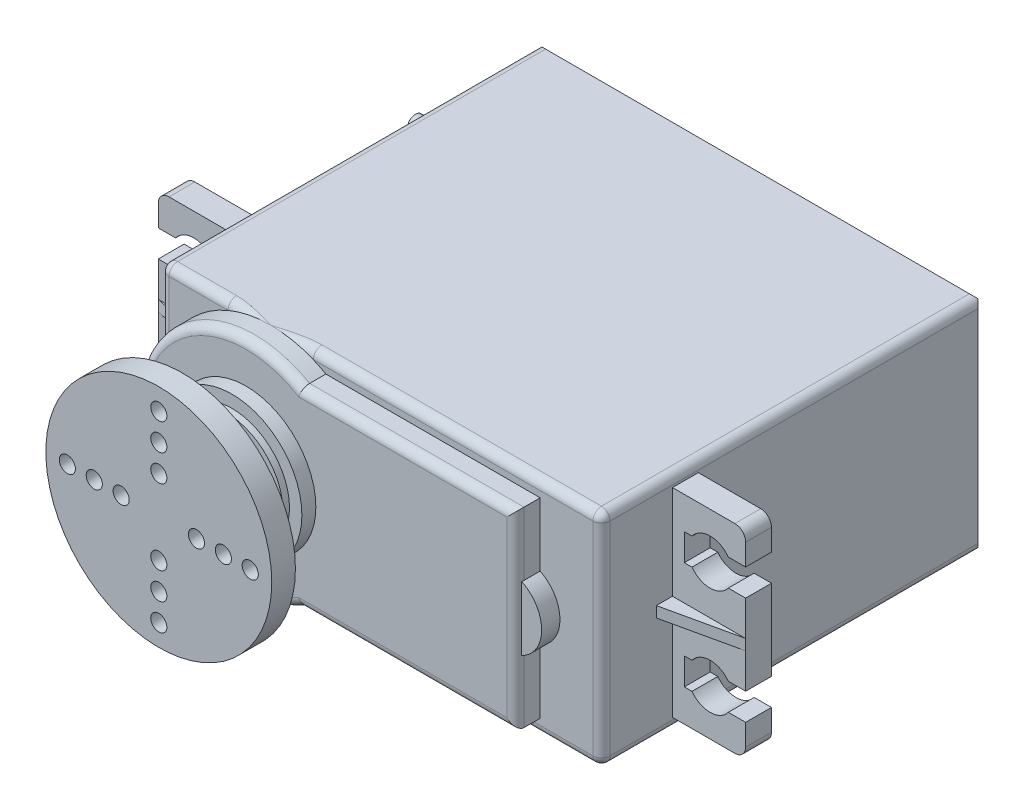
SolidWorks part; units mm, degrees
material "Cast Alloy Steel"
ref_plane "Front Plane" through (0, 0, 0) normal (0, 0, 1) x (1, 0, 0)
ref_plane "Top Plane" through (0, 0, 0) normal (0, 1, 0) x (1, 0, 0)
ref_plane "Right Plane" through (0, 0, 0) normal (1, 0, 0) x (0, 0, -1)
sketch "Sketch1" plane through (0, 0, 0) normal (0, 0, 1) x (1, 0, 0)
  line L1 (-20.5, 10.25) -> (20.5, 10.25)
  line L2 (-20.5, 10.25) -> (-20.5, -10.25)
  line L3 (-20.5, -10.25) -> (20.5, -10.25)
  line L4 (20.5, 10.25) -> (20.5, -10.25)
  line L5 (-20.5, 10.25) -> (20.5, -10.25) construction
  line L6 (-20.5, -10.25) -> (20.5, 10.25) construction
  point P0 (0, 0)
  dimension "D1" = 41
  dimension "D2" = 20.5
extrude "Boss-Extrude1" add sketch "Sketch1" along normal blind 37
chamfer "Chamfer1" distance 2 angle 45 4 edges at (-20.5, 0, 0) (0, 10.25, 0) (20.5, 0, 0) (0, -10.25, 0)
sketch "Sketch2" plane through (0, 0, 37) normal (0, 0, 1) x (1, 0, 0)
  line L0 (-20.5, 10.25) -> (-20.5, -10.25) construction
  line L1 (-5.122, 8.875) -> (14.8, 8.875)
  line L3 (-5.122, -8.875) -> (14.8, -8.875)
  line L4 (14.8, 8.875) -> (14.8, 2.9719)
  line L5 (-20.5, 0) -> (20.5, 0) construction
  line L6 (20.5, -10.25) -> (20.5, 10.25) construction
  line L7 (14.8, -2.9719) -> (14.8, -8.875)
  line L8 (14.8, 2.9719) -> (14.8, -2.9719) construction
  arc A0 (-5.122, 8.875) -> (-5.122, -8.875) centre (-10.25, 0) ccw
  arc A1 (14.8, -2.9719) -> (14.8, 2.9719) centre (13.32, 0) ccw
  dimension "D2" = 6.64
  dimension "D5" = 1.48
  dimension "D1" = 10.25
  dimension "D3" = 5.7
  dimension "D4" = 17.75
extrude "Boss-Extrude2" add sketch "Sketch2" along normal blind 2.3
sketch "Sketch3" plane through (0, 0, 39.3) normal (0, 0, 1) x (1, 0, 0)
  line L0 (14.8, 2.9719) -> (14.8, -2.9719)
  arc A0 (14.8, -2.9719) -> (14.8, 2.9719) centre (13.32, 0) ccw construction
  arc A1 (14.8, -2.9719) -> (14.8, 2.9719) centre (13.32, 0) ccw
extrude "Cut-Extrude1" cut sketch "Sketch3" against normal blind 0.6
sketch "Sketch4" plane through (0, 0, 39.3) normal (0, 0, 1) x (1, 0, 0)
  circle A0 centre (-10.25, 0) radius 6.5
  dimension "D1" = 13
extrude "Boss-Extrude3" add sketch "Sketch4" along normal blind 1.3
sketch "Sketch5" plane through (0, 0, 40.6) normal (0, 0, 1) x (1, 0, 0)
  circle A0 centre (-10.25, 0) radius 5.35
  dimension "D1" = 10.7
extrude "Boss-Extrude4" add sketch "Sketch5" along normal blind 0.6
sketch "Sketch6" plane through (0, 0, 41.2) normal (0, 0, 1) x (1, 0, 0)
  circle A0 centre (-10.25, 0) radius 3
  dimension "D1" = 6
extrude "Boss-Extrude5" add sketch "Sketch6" along normal blind 4
sketch "Sketch7" plane through (0, 0, 45.2) normal (0, 0, 1) x (1, 0, 0)
  circle A0 centre (-10.25, 0) radius 10.5
  dimension "D1" = 21
extrude "Boss-Extrude6" add sketch "Sketch7" along normal blind 2.2
sketch "Sketch8" plane through (0, 0, 47.4) normal (0, 0, 1) x (1, 0, 0)
  line L0 (-10.25, 0) -> (-20.75, 0) construction
  circle A0 centre (-10.25, 0) radius 10.5 construction
  circle A1 centre (-13.75, 0) radius 0.75
  circle A2 centre (-16.25, 0) radius 0.75
  circle A3 centre (-18.75, 0) radius 0.75
  dimension "D1" = 1.5
  dimension "D2" = 3.5
  dimension "D3" = 2.5
  dimension "D4" = 2.5
extrude "Cut-Extrude2" cut sketch "Sketch8" against normal blind 2.2
pattern_circular "CirPattern1" count 4 over 360 about axis through (-10.25, 0, 47.4) along (0, 0, -1) of "Cut-Extrude2"
sketch "Sketch9" plane through (-20.5, 0, 0) normal (-1, 0, 0) x (0, 0, 1)
  line L1 (3.2, 3.5) -> (7.4, 3.5)
  line L2 (3.2, 3.5) -> (3.2, -3.5)
  line L3 (3.2, -3.5) -> (7.4, -3.5)
  line L4 (7.4, 3.5) -> (7.4, -3.5)
  point P4 (3.2, 0)
  dimension "D1" = 7
  dimension "D2" = 4.2
  dimension "D3" = 3.2
extrude "Boss-Extrude7" add sketch "Sketch9" along normal blind 1
sketch "Sketch10" plane through (-21.5, 0, 0) normal (-1, 0, 0) x (0, 0, 1)
  line L8 (3.55, 3.15) -> (3.55, -3.15)
  line L9 (3.55, -3.15) -> (7.05, -3.15)
  line L10 (7.05, -3.15) -> (7.05, 3.15)
  line L11 (7.05, 3.15) -> (3.55, 3.15)
  line L12 (3.55, 3.15) -> (3.55, -3.15)
  line L13 (3.55, -3.15) -> (7.05, -3.15)
  line L14 (7.05, -3.15) -> (7.05, 3.15)
  line L15 (7.05, 3.15) -> (3.55, 3.15)
  dimension "D1" = 0.35
extrude "Boss-Extrude8" add sketch "Sketch10" along normal blind 4 draft 5
sketch "Sketch11" plane through (-25.5, 0, 0) normal (-1, 0, 0) x (0, 0, 1)
  line L0 (3.9, 2.8) -> (3.9, -2.8) construction
  circle A0 centre (5.3, 1.5) radius 0.75
  circle A1 centre (5.3, 0) radius 0.75
  circle A2 centre (5.3, -1.5) radius 0.75
  dimension "D1" = 1.5
  dimension "D2" = 1.4
  dimension "D3" = 1.4
  dimension "D4" = 1.4
extrude "Boss-Extrude10" add sketch "Sketch11" along normal blind 3 separate body contours A1 | A2 | A0 region at (-25.5, 1.5, 5.3) region at (-25.5, -1.5, 5.3) region at (-25.5, 0, 5.3)
fillet "Fillet1" radius 0.8 15 edges at (-20.5, -5.125, 37) (-15.375, -10.25, 37) (-15.375, 10.25, 37) (-20.5, 5.125, 37) (5.125, -10.25, 37) (20.5, 0, 37) (5.125, 10.25, 37) (14.8, 0, 39.3) (4.839, -8.875, 39.3) (-20.5, 0, 39.3) (4.839, 8.875, 39.3) (20.5, -10.25, 19.5) (20.5, 10.25, 19.5) (-20.5, 10.25, 19.5) (-20.5, -10.25, 19.5)
sketch "Sketch12" plane through (-20.5, 0, 0) normal (-1, 0, 0) x (0, 0, 1)
  line L0 (36.2, -9.45) -> (36.2, -3.9699) construction
  line L1 (28, 9.25) -> (30.4, 9.25)
  line L2 (28, 9.25) -> (28, -9.25)
  line L3 (28, -9.25) -> (30.4, -9.25)
  line L4 (30.4, 9.25) -> (30.4, -9.25)
  line L6 (2, 10.25) -> (36.2, 10.25) construction
  dimension "D1" = 18.5
  dimension "D2" = 2.4
  dimension "D3" = 5.8
  dimension "D4" = 1
extrude "Boss-Extrude11" add sketch "Sketch12" along normal blind 6.8
fillet "Fillet2" radius 1 2 edges at (-27.3, -9.25, 29.2) (-27.3, 9.25, 29.2)
sketch "Sketch13" plane through (0, 0, 30.4) normal (0, 0, 1) x (1, 0, 0)
  line L0 (-27.3, -8.25) -> (-27.3, 8.25) construction
  line L1 (-27.3, 6.25) -> (-25.6875, 6.25)
  line L2 (-27.3, 6.25) -> (-27.3, 3.75)
  line L3 (-27.3, 3.75) -> (-25.6875, 3.75)
  line L4 (-21.6, 6.25) -> (-21.6, 3.75)
  line L5 (-27.3, 0) -> (-20.75, 0) construction
  line L6 (-22.3125, 6.25) -> (-21.6, 6.25)
  line L7 (-22.3125, 3.75) -> (-21.6, 3.75)
  line L8 (-22.3125, -3.75) -> (-21.6, -3.75)
  line L9 (-22.3125, -6.25) -> (-21.6, -6.25)
  line L10 (-21.6, -6.25) -> (-21.6, -3.75)
  line L11 (-27.3, -3.75) -> (-25.6875, -3.75)
  line L12 (-27.3, -6.25) -> (-27.3, -3.75)
  line L13 (-27.3, -6.25) -> (-25.6875, -6.25)
  arc A0 (-25.6875, 3.75) -> (-22.3125, 3.75) centre (-24, 5) ccw
  circle A1 centre (-10.25, 0) radius 10.5 construction
  arc A2 (-22.3125, 6.25) -> (-25.6875, 6.25) centre (-24, 5) ccw
  arc A3 (-22.3125, -6.25) -> (-25.6875, -6.25) centre (-24, -5) cw
  arc A4 (-25.6875, -3.75) -> (-22.3125, -3.75) centre (-24, -5) cw
  point P13 (-27.3, 5)
  dimension "D2" = 4.2
  dimension "D1" = 2.5
  dimension "D3" = 3.3
  dimension "D4" = 5.7
  dimension "D5" = 5
extrude "Cut-Extrude3" cut sketch "Sketch13" against normal blind 6.8
sketch "Sketch17" plane through (0, 0, 0) normal (0, 1, 0) x (1, 0, 0)
  line L0 (-27.3, -30.4) -> (-20.5, -31.9)
  line L1 (-20.5, -2) -> (-20.5, -36.2) construction
  line L2 (-20.5, -31.9) -> (-20.5, -30.4)
  line L3 (-20.5, -30.4) -> (-27.3, -30.4)
  dimension "D1" = 1.5
extrude "Boss-Extrude12" add sketch "Sketch17" along normal mid plane 1
ref_plane "Plane1" through (0, 0, 0) normal (-1, 0, 0) x (0, 0, 1)
mirror "Mirror1" about plane through (0, 0, 0) normal (-1, 0, 0) of "Boss-Extrude12", "Cut-Extrude3", "Fillet2", "Boss-Extrude11"
